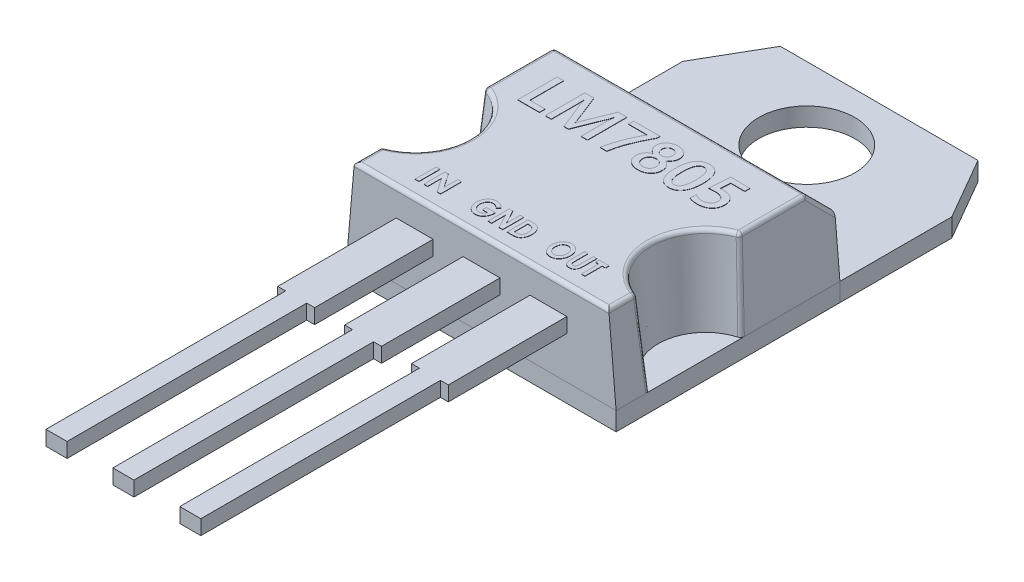
SolidWorks part; units mm, degrees
ref_plane "Front Plane" through (0, 0, 0) normal (0, 0, 1) x (1, 0, 0)
ref_plane "Top Plane" through (0, 0, 0) normal (0, 1, 0) x (1, 0, 0)
ref_plane "Right Plane" through (0, 0, 0) normal (1, 0, 0) x (0, 0, -1)
sketch "Sketch1" plane through (0, 0, 0) normal (0, 1, 0) x (1, 0, 0)
  line L1 (-5.11, -7.55) -> (5.11, -7.55)
  line L2 (-5.11, -7.55) -> (-5.11, 7.55)
  line L3 (-5.11, 7.55) -> (5.11, 7.55)
  line L4 (5.11, -7.55) -> (5.11, 7.55)
  line L5 (-5.11, -7.55) -> (5.11, 7.55) construction
  line L6 (-5.11, 7.55) -> (5.11, -7.55) construction
  circle A0 centre (0, 4.8) radius 1.825
  point P0 (0, 0)
  dimension "D3" = 3.65
  dimension "D1" = 10.22
  dimension "D2" = 15.1
  dimension "D4" = 2.75
extrude "Boss-Extrude1" add sketch "Sketch1" along normal blind 0.7
chamfer "Chamfer1" distance 2.35 angle 30 2 edges at (-5.11, 0.35, -7.55) (5.11, 0.35, -7.55) first distance on face at (-5.11, 0.35, 0) first distance on face at (5.11, 0.35, 0)
sketch "Sketch2" plane through (0, 0.7, 0) normal (0, 1, 0) x (1, 0, 0)
  line L0 (5.11, -7.55) -> (5.11, 5.2) construction
  line L1 (-5.11, -7.55) -> (5.11, -7.55)
  line L2 (-5.11, -7.55) -> (-5.11, -6.305)
  line L3 (-5.11, 0.95) -> (5.11, 0.95)
  line L4 (5.11, -7.55) -> (5.11, -6.305)
  line L5 (0, 0) -> (0, -2.795) construction
  line L6 (-5.11, -2.795) -> (-5.11, 0.95)
  line L7 (5.11, -2.795) -> (5.11, 0.95)
  arc A0 (-5.11, -2.795) -> (-5.11, -6.305) centre (-5.51, -4.55) cw
  arc A1 (5.11, -2.795) -> (5.11, -6.305) centre (5.51, -4.55) ccw
  point P10 (-3.71, -4.55)
  dimension "D2" = 3
  dimension "D3" = 1.8
  dimension "D1" = 8.5
  dimension "D4" = 1.4
extrude "Boss-Extrude2" add sketch "Sketch2" along normal blind 3.2 separate body
chamfer "Chamfer2" distance 3.2 angle 5 6 edges at (5.11, 3.9, 6.9275) (3.71, 3.9, 4.55) (5.11, 3.9, 0.9225) (-5.11, 3.9, 0.9225) (-3.71, 3.9, 4.55) (-5.11, 3.9, 6.9275) first distance on face at (5.11, 2.3, 6.9275) first distance on face at (4.41, 2.3, 4.55) first distance on face at (5.11, 2.3, 0.9225) first distance on face at (-5.11, 2.3, 0.9225) first distance on face at (-4.41, 2.3, 4.55) first distance on face at (-5.11, 2.3, 6.9275)
chamfer "Chamfer3" distance 1 angle 45 1 edges at (0, 3.9, -0.95)
fillet "Fillet1" radius 0.15 15 edges at (0, 2.9, -0.95) (-4.8738, 3.4, -0.45) (-4.83, 3.9, 1.3172) (-3.43, 3.9, 4.55) (-4.83, 3.9, 7.0328) (0, 3.9, 0.05) (4.8738, 3.4, -0.45) (4.83, 3.9, 1.3172) (0, 3.9, 7.55) (4.83, 3.9, 7.0328) (3.43, 3.9, 4.55)
sketch "Sketch3" plane through (0, 0, 7.55) normal (0, 0, 1) x (1, 0, 0)
  line L0 (0, 0) -> (0, 2.58) construction
  line L1 (-0.7, 2.3) -> (0.7, 2.3)
  line L2 (-0.7, 2.3) -> (-0.7, 2.86)
  line L3 (-0.7, 2.86) -> (0.7, 2.86)
  line L4 (0.7, 2.3) -> (0.7, 2.86)
  line L5 (-0.7, 2.3) -> (0.7, 2.86) construction
  line L6 (-0.7, 2.86) -> (0.7, 2.3) construction
  line L7 (-5.11, 0) -> (5.11, 0) construction
  point P0 (0, 2.58)
  dimension "D1" = 1.4
  dimension "D2" = 0.56
  dimension "D3" = 2.3
extrude "Boss-Extrude3" add sketch "Sketch3" along normal blind 4.5 separate body
sketch "Sketch4" plane through (0, 0, 12.05) normal (0, 0, 1) x (1, 0, 0)
  line L0 (0.7, 2.86) -> (-0.7, 2.86) construction
  line L1 (-0.4, 2.3) -> (0.4, 2.3)
  line L2 (-0.4, 2.3) -> (-0.4, 2.86)
  line L3 (-0.4, 2.86) -> (0.4, 2.86)
  line L4 (0.4, 2.3) -> (0.4, 2.86)
  line L5 (-0.4, 2.3) -> (0.4, 2.86) construction
  line L6 (-0.4, 2.86) -> (0.4, 2.3) construction
  line L7 (-0.7, 2.3) -> (0.7, 2.3) construction
  point P0 (0, 2.58)
  dimension "D1" = 0.8
extrude "Boss-Extrude4" add sketch "Sketch4" along normal blind 9.1
pattern_linear "LPattern1" count 2 spacing 2.54 along (-1, 0, 0) count 2 spacing 2.54 along (1, 0, 0) of bodies 104
sketch "Sketch5" plane through (0, 3.9, 0) normal (0, 1, 0) x (1, 0, 0)
  text T0 "<b>LM7805</b>" font "Yu Gothic UI" height 1.5
extrude "Boss-Extrude5" add sketch "Sketch5" along normal blind 0.01
sketch "Sketch7" plane through (0, 0.7, 0) normal (0, 1, 0) x (1, 0, 0)
  line L6 (-5.11, 0.95) -> (-5.11, -2.6796)
  line L7 (5.11, 0.95) -> (-5.11, 0.95)
  line L8 (5.11, -2.6796) -> (5.11, 0.95)
  line L9 (5.11, -7.55) -> (5.11, -6.4204)
  line L10 (-5.11, -7.55) -> (5.11, -7.55)
  line L11 (-5.11, -6.4204) -> (-5.11, -7.55)
  line L12 (-5.11, 0.95) -> (-5.11, -2.6796)
  line L13 (5.11, 0.95) -> (-5.11, 0.95)
  line L14 (5.11, -2.6796) -> (5.11, 0.95)
  line L15 (5.11, -7.55) -> (5.11, -6.4204)
  line L16 (-5.11, -7.55) -> (5.11, -7.55)
  line L17 (-5.11, -6.4204) -> (-5.11, -7.55)
  arc A6 (-5.0027, -6.277) -> (-5.0027, -2.823) centre (-5.51, -4.55) ccw
  arc A7 (-5.11, -2.6796) -> (-5.0027, -2.823) centre (-4.9607, -2.6797) ccw
  arc A8 (5.0027, -2.823) -> (5.11, -2.6796) centre (4.9607, -2.6797) ccw
  arc A9 (5.0027, -2.823) -> (5.0027, -6.277) centre (5.51, -4.55) ccw
  arc A10 (5.11, -6.4204) -> (5.0027, -6.277) centre (4.9607, -6.4203) ccw
  arc A11 (-5.0027, -6.277) -> (-5.11, -6.4204) centre (-4.9607, -6.4203) ccw
  arc A12 (-5.0027, -6.277) -> (-5.0027, -2.823) centre (-5.51, -4.55) ccw
  arc A13 (-5.11, -2.6796) -> (-5.0027, -2.823) centre (-4.9607, -2.6797) ccw
  arc A14 (5.0027, -2.823) -> (5.11, -2.6796) centre (4.9607, -2.6797) ccw
  arc A15 (5.0027, -2.823) -> (5.0027, -6.277) centre (5.51, -4.55) ccw
  arc A16 (5.11, -6.4204) -> (5.0027, -6.277) centre (4.9607, -6.4203) ccw
  arc A17 (-5.0027, -6.277) -> (-5.11, -6.4204) centre (-4.9607, -6.4203) ccw
  dimension "D1" = 0
split line "Split Line1"
sketch "Sketch8" plane through (-5.11, 0, 0) normal (-1, 0, 0) x (0, 0, 1)
  line L0 (-0.95, 0.7) -> (-0.95, 0)
  line L1 (-5.2, 0) -> (7.55, 0) construction
split line "Split Line2"
sketch "Sketch9" plane through (0, 3.9, 0) normal (0, 1, 0) x (1, 0, 0)
  text T0 "<b>IN</b>" font "Century Gothic" height 0.8
  text T1 "<b>OUT</b>" font "Century Gothic" height 0.8
  text T2 "<b>GND</b>" font "Century Gothic" height 0.8
extrude "Boss-Extrude6" add sketch "Sketch9" along normal blind 0.01
